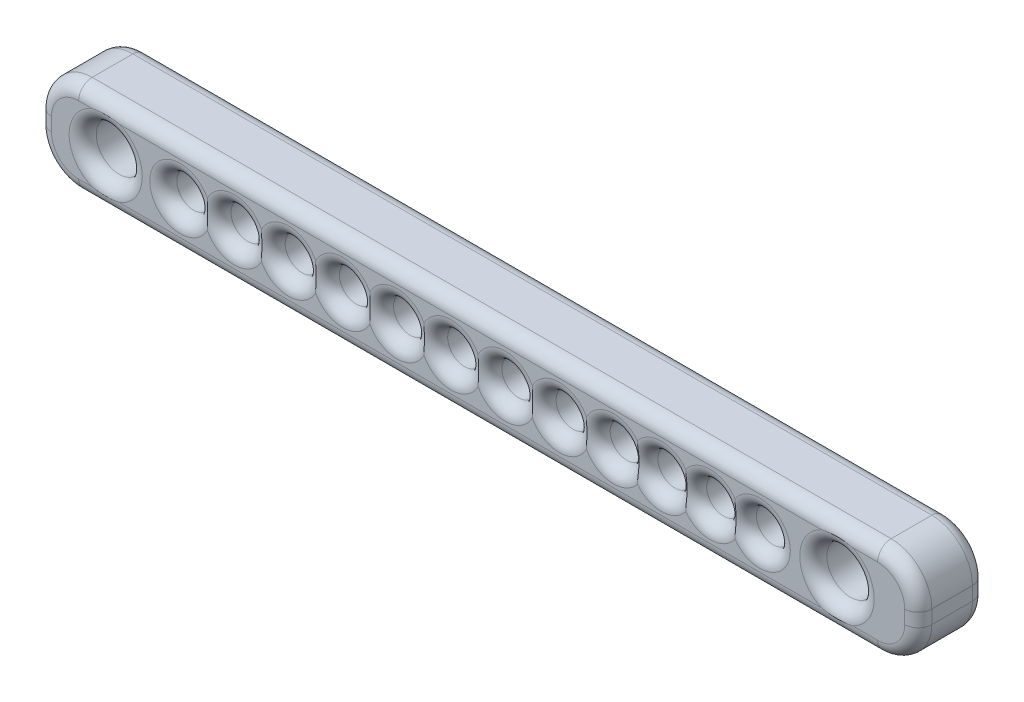
SolidWorks part; units mm, degrees
ref_plane "Front Plane" through (0, 0, 0) normal (0, 0, 1) x (1, 0, 0)
ref_plane "Top Plane" through (0, 0, 0) normal (0, 1, 0) x (1, 0, 0)
ref_plane "Right Plane" through (0, 0, 0) normal (1, 0, 0) x (0, 0, -1)
sketch "草圖1" plane through (0, 0, 0) normal (0, 0, 1) x (1, 0, 0)
  line L1 (32.5, -3.5) -> (-32.5, -3.5)
  line L2 (32.5, -3.5) -> (32.5, 3.5)
  line L3 (32.5, 3.5) -> (-32.5, 3.5)
  line L4 (-32.5, -3.5) -> (-32.5, 3.5)
  line L5 (32.5, -3.5) -> (-32.5, 3.5) construction
  line L6 (32.5, 3.5) -> (-32.5, -3.5) construction
  circle A0 centre (-27.5, 0) radius 1.7
  circle A4 centre (-22, 0) radius 1.25
  circle A5 centre (-18, 0) radius 1.25
  circle A6 centre (-14, 0) radius 1.25
  circle A7 centre (-10, 0) radius 1.25
  circle A8 centre (-6, 0) radius 1.25
  circle A9 centre (-2, 0) radius 1.25
  circle A10 centre (2, 0) radius 1.25
  circle A11 centre (6, 0) radius 1.25
  circle A12 centre (10, 0) radius 1.25
  circle A13 centre (26.5, 0) radius 1.75
  circle A14 centre (20.8016, 0) radius 1.25
  circle A15 centre (17.1276, 0) radius 1.25
  circle A16 centre (13.53, 0) radius 1.25
  point P0 (0, 0)
  point P14 (19.73, 0)
  point P15 (15.8263, 0)
  point P36 (12.9942, 0)
  point P37 (21.2609, 0)
  point P38 (17.1276, 0)
  point P39 (13.53, 0)
  point P40 (20.8016, 0)
  dimension "D8" = 3.5
  dimension "D1" = 65
  dimension "D2" = 7
  dimension "D4" = 54
  dimension "D5" = 5
extrude "填料-伸長1" add sketch "草圖1" along normal blind 5
fillet "圓角1" radius 3 4 edges at (-32.5, -3.5, 2.5) (-32.5, 3.5, 2.5) (32.5, -3.5, 2.5) (32.5, 3.5, 2.5)
fillet "圓角2" radius 1 44 edges at (28.25, 0, 0) (11.25, 0, 0) (7.25, 0, 0) (3.25, 0, 0) (-0.75, 0, 0) (-4.75, 0, 0) (-8.75, 0, 0) (-12.75, 0, 0) (-16.75, 0, 0) (-20.75, 0, 0) (22.0516, 0, 0) (-25.8, 0, 0) (31.6213, -2.6213, 0) (32.5, 0, 0) (31.6213, 2.6213, 0) (0, 3.5, 0) (-31.6213, 2.6213, 0) (-32.5, 0, 0) (-31.6213, -2.6213, 0) (0, -3.5, 0) (28.25, 0, 5) (7.25, 0, 5) (-0.75, 0, 5) (-8.75, 0, 5) (-16.75, 0, 5) (22.0516, 0, 5) (-31.6213, 2.6213, 5) (0, 3.5, 5) (31.6213, 2.6213, 5) (32.5, 0, 5) (31.6213, -2.6213, 5) (0, -3.5, 5) (-31.6213, -2.6213, 5) (-32.5, 0, 5) (-25.8, 0, 5) (-20.75, 0, 5) (-12.75, 0, 5) (-4.75, 0, 5) (3.25, 0, 5) (11.25, 0, 5) (14.78, 0, 0) (18.3776, 0, 0) (14.78, 0, 5) (18.3776, 0, 5)
